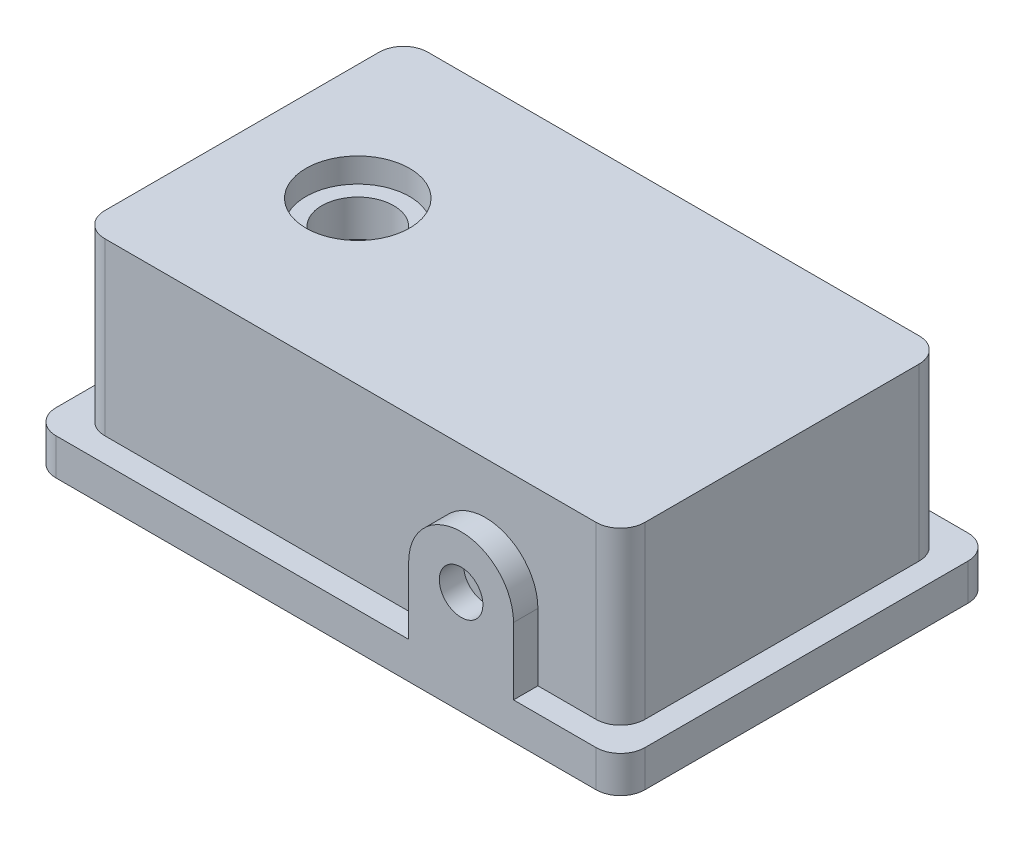
SolidWorks part; units mm, degrees
ref_plane "前视基准面" through (0, 0, 0) normal (0, 0, 1) x (1, 0, 0)
ref_plane "上视基准面" through (0, 0, 0) normal (0, 1, 0) x (1, 0, 0)
ref_plane "右视基准面" through (0, 0, 0) normal (1, 0, 0) x (0, 0, -1)
other "Configuration Table"
sketch "草图1" plane through (0, 0, 0) normal (0, 1, 0) x (1, 0, 0)
  line L1 (0, 0) -> (-483, 0)
  line L2 (0, 0) -> (0, 305)
  line L3 (0, 305) -> (-483, 305)
  line L4 (-483, 0) -> (-483, 305)
  dimension "D1" = 483
  dimension "D2" = 305
extrude "凸台-拉伸1" add sketch "草图1" along normal blind 30
sketch "草图2" plane through (0, 30, 0) normal (0, 1, 0) x (1, 0, 0)
  line L0 (-483, 0) -> (0, 0) construction
  line L1 (-463, 285) -> (-20, 285)
  line L2 (-463, 285) -> (-463, 20)
  line L3 (-463, 20) -> (-20, 20)
  line L4 (-20, 285) -> (-20, 20)
  line L5 (-483, 305) -> (-483, 0) construction
  line L6 (0, 305) -> (-483, 305) construction
  line L7 (0, 0) -> (0, 305) construction
  dimension "D1" = 20
  dimension "D2" = 20
  dimension "D3" = 20
  dimension "D4" = 20
extrude "凸台-拉伸2" add sketch "草图2" along normal blind 140
fillet "圆角2" radius 20 8 edges at (-20, 100, -285) (-483, 15, 0) (0, 15, 0) (-20, 100, -20) (0, 15, -305) (-463, 100, -20) (-483, 15, -305) (-463, 100, -285)
sketch "草图5" plane through (0, 170, 0) normal (0, 1, 0) x (1, 0, 0)
  line L8 (-40, 40) -> (-40, 265)
  line L9 (-40, 265) -> (-443, 265)
  line L10 (-443, 265) -> (-443, 40)
  line L11 (-443, 40) -> (-40, 40)
  line L12 (-40, 60) -> (-40, 245)
  line L13 (-60, 265) -> (-423, 265)
  line L14 (-443, 245) -> (-443, 60)
  line L15 (-423, 40) -> (-60, 40)
  arc A4 (-40, 245) -> (-60, 265) centre (-60, 245) ccw
  arc A5 (-40, 60) -> (-60, 40) centre (-60, 60) cw
  arc A6 (-443, 60) -> (-423, 40) centre (-423, 60) ccw
  arc A7 (-423, 265) -> (-443, 245) centre (-423, 245) ccw
  dimension "D2" = 20
  dimension "D1" = 20
extrude "切除-拉伸3" cut sketch "草图5" against normal through all from offset 20 offset against normal yes
sketch "草图7" plane through (0, 170, 0) normal (0, 1, 0) x (1, 0, 0)
  line L1 (-463, 152.5) -> (-96.2701, 152.5) construction
  line L2 (-463, 265) -> (-463, 40) construction
  line L3 (-40, 285) -> (-443, 285) construction
  line L4 (-241.5, 285) -> (-241.5, 49.5717) construction
  line L5 (-463, 207.5) -> (-368, 207.5)
  line L6 (-463, 97.5) -> (-368, 97.5)
  circle A0 centre (-368, 152.5) radius 29.5
  circle A1 centre (-368, 152.5) radius 42.5
  arc A2 (-368, 97.5) -> (-368, 207.5) centre (-368, 152.5) ccw
  line M5 (-463, 265) -> (-463, 40)
  dimension "D1" = 85
  dimension "D2" = 59
  dimension "D3" = 126.5
  dimension "D4" = 55
  dimension "D5" = 55
extrude "凸台-拉伸3" add sketch "草图7" against normal blind 50 contours L6 A2 L5 A1 M5 | A1 A0 region at (-415.5, 170, -205.6399) region at (-409.2979, 170, -152.5)
extrude "切除-拉伸5" cut sketch "草图7<5>" against normal blind 20 contours A1 A0 region at (-409.2979, 170, -152.5)
sketch "草图7<5>" plane through (0, 170, 0) normal (0, 1, 0) x (1, 0, 0) same geometry as "草图7"
extrude "切除-拉伸6" cut sketch "草图7<6>" against normal blind 40 contours A0 region at (-368, 170, -152.5)
sketch "草图7<6>" plane through (0, 170, 0) normal (0, 1, 0) x (1, 0, 0) same geometry as "草图7"
sketch "草图9" plane through (0, 0, -20) normal (0, 0, 1) x (1, 0, 0)
  line L0 (-443, 170) -> (-40, 170) construction
  line L1 (-241.5, 170) -> (-241.5, -11.9161) construction
  line L2 (-241.5, 170) -> (-20, 170)
  line L3 (-130.75, 170) -> (-130.75, -28.0147) construction
  line L4 (-443, 30) -> (-40, 30) construction
  line L5 (-87.75, 85) -> (-87.75, 30)
  line L6 (-87.75, 30) -> (-173.75, 30)
  line L7 (-173.75, 30) -> (-173.75, 85)
  circle A0 centre (-130.75, 85) radius 17.8767
  arc A2 (-173.75, 85) -> (-87.75, 85) centre (-130.75, 85) cw
  line M9 (-443, 30) -> (-40, 30)
  dimension "D2" = 35.7534
  dimension "D3" = 43
  dimension "D1" = 55
ref_plane "基准面1" through (0, 30, -20) normal (0, -1, 0) x (-1, 0, 0)
extrude "凸台-拉伸4" add sketch "草图9" along normal up to surface (20 mm away) contours A2 L7 L5 A0 M9 region at (-89.0538, 57.5, -20) up to face at (-241.5, 15, 0)
